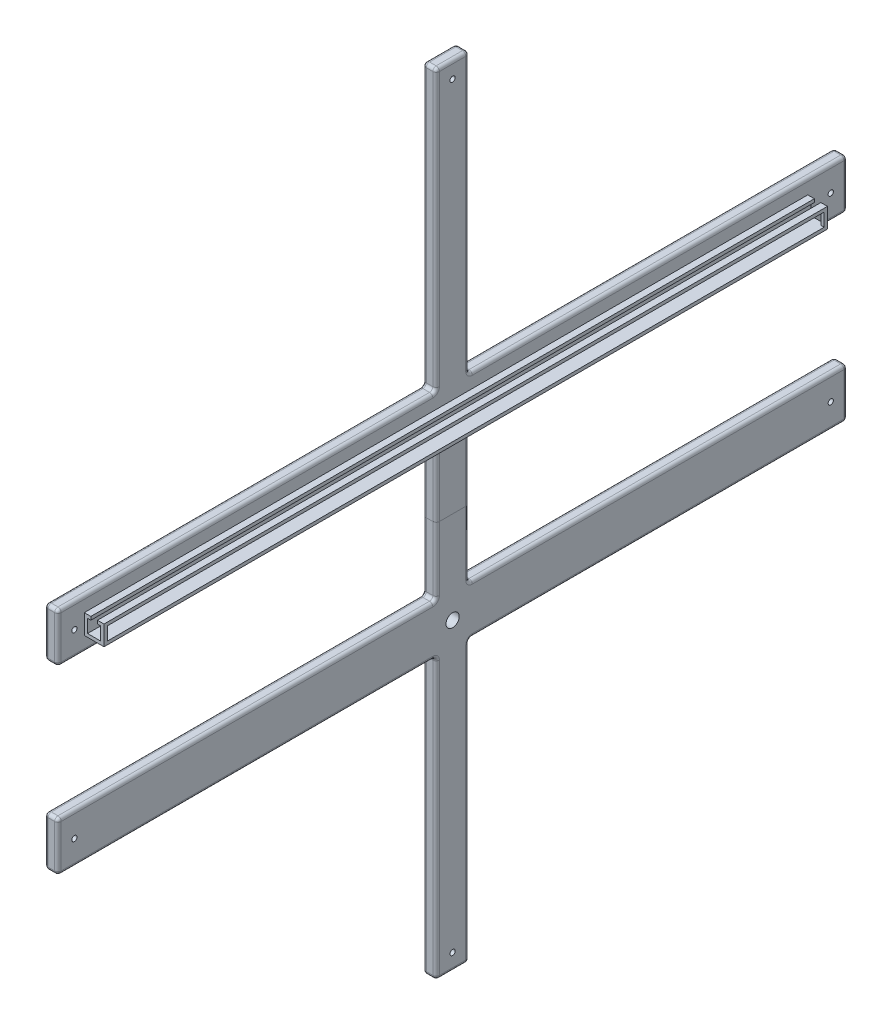
SolidWorks part; units mm, degrees
ref_plane "Front Plane" through (0, 0, 0) normal (0, 0, 1) x (1, 0, 0)
ref_plane "Top Plane" through (0, 0, 0) normal (0, 1, 0) x (1, 0, 0)
ref_plane "Right Plane" through (0, 0, 0) normal (1, 0, 0) x (0, 0, -1)
sketch "Sketch3" plane through (0, 0, 0) normal (1, 0, 0) x (0, 0, -1)
  line L0 (-151.0311, 58.4862) -> (-36.0311, 58.4862)
  line L1 (-276.0311, 3.4862) -> (-161.0311, 3.4862)
  line L2 (-276.0311, 3.4862) -> (-276.0311, -11.5138)
  line L3 (-276.0311, -11.5138) -> (-161.0311, -11.5138)
  line L4 (-36.0311, 3.4862) -> (-36.0311, -11.5138)
  line L5 (-276.0311, 58.4862) -> (-161.0311, 58.4862)
  line L6 (-276.0311, 58.4862) -> (-276.0311, 43.4862)
  line L7 (-276.0311, 43.4862) -> (-161.0311, 43.4862)
  line L8 (-36.0311, 58.4862) -> (-36.0311, 43.4862)
  line L9 (-161.0311, 143.4862) -> (-151.0311, 143.4862)
  line L10 (-161.0311, 143.4862) -> (-161.0311, 58.4862)
  line L11 (-161.0311, -96.5138) -> (-151.0311, -96.5138)
  line L12 (-151.0311, 143.4862) -> (-151.0311, 58.4862)
  line L13 (-151.0311, 43.4862) -> (-36.0311, 43.4862)
  line L14 (-161.0311, 43.4862) -> (-161.0311, 3.4862)
  line L15 (-151.0311, 43.4862) -> (-151.0311, 3.4862)
  line L16 (-151.0311, 3.4862) -> (-36.0311, 3.4862)
  line L17 (-151.0311, -11.5138) -> (-36.0311, -11.5138)
  line L18 (-161.0311, -11.5138) -> (-161.0311, -96.5138)
  line L19 (-151.0311, -11.5138) -> (-151.0311, -96.5138)
  line L20 (-398.8778, 23.4862) -> (82.314, 23.4862) construction
  circle A0 centre (-156.0311, -91.5138) radius 0.8
  circle A2 centre (-156.0311, 138.4862) radius 0.8
  dimension "D9" = 115
  dimension "D13" = 1.6
  dimension "D14" = 5
  dimension "D1" = 240
  dimension "D2" = 240
  dimension "D3" = 240
  dimension "D4" = 10
  dimension "D5" = 15
  dimension "D6" = 15
  dimension "D7" = 85
  dimension "D8" = 85
  dimension "D10" = 115
  dimension "D11" = 115
  dimension "D12" = 40
  dimension "D15" = 5
  dimension "D16" = 120
extrude "Boss-Extrude1" add sketch "Sketch3" along normal blind 4 contours L12 L0 L8 L13 L15 L16 L4 L17 L19 L11 L18 L3 L2 L1 L14 L7 L6 L5 L10 L9
sketch "Sketch4" plane through (0, 0, 0) normal (1, 0, 0) x (0, 0, -1)
  line L0 (-161.0311, -96.5138) -> (-151.0311, -96.5138) construction
  line L1 (-161.0311, -11.5138) -> (-161.0311, -96.5138) construction
  line L2 (-316.8277, 23.4862) -> (27.7287, 23.4862) construction
  line L3 (-161.0311, 143.4862) -> (-151.0311, 143.4862) construction
  line L4 (-156.0311, 175.0015) -> (-156.0311, -131.8525) construction
  line L5 (-151.0311, 143.4862) -> (-151.0311, 58.4862) construction
  line L6 (-276.0311, 3.4862) -> (-276.0311, -11.5138) construction
  line L7 (-276.0311, 3.4862) -> (-161.0311, 3.4862) construction
  line L11 (-276.0311, -11.5138) -> (-161.0311, -11.5138) construction
  line L12 (-161.0311, 43.4862) -> (-161.0311, 3.4862) construction
  circle A0 centre (-156.0311, -91.5138) radius 0.8
  circle A1 centre (-156.0311, 138.4862) radius 0.8
  circle A2 centre (-271.0311, -4.0138) radius 0.8
  circle A3 centre (-271.0311, 50.9862) radius 0.8
  circle A4 centre (-41.0311, -4.0138) radius 0.8
  circle A5 centre (-41.0311, 50.9862) radius 0.8
  circle A6 centre (-156.0311, -4.0138) radius 2
  circle A7 centre (-156.0311, 50.9862) radius 2
  point P10 (-156.0311, 143.4862)
  point P17 (-151.0311, 100.9862)
  dimension "D1" = 1.6
  dimension "D3" = 5
  dimension "D6" = 5
  dimension "D8" = 1.6
  dimension "D9" = 4
  dimension "D10" = 7.5
  dimension "D2" = 5
  dimension "D4" = 120
  dimension "D5" = 5
  dimension "D7" = 7.5
  dimension "D11" = 5
extrude "Cut-Extrude1" cut sketch "Sketch4" against normal blind 4 and the other way blind 4
fillet "Fillet1" radius 1 60 edges at (2, 143.4862, 161.0311) (2, 58.4862, 161.0311) (2, 58.4862, 276.0311) (2, 43.4862, 276.0311) (2, 43.4862, 161.0311) (2, 3.4862, 161.0311) (2, 3.4862, 276.0311) (2, -11.5138, 276.0311) (2, -11.5138, 161.0311) (2, -96.5138, 161.0311) (2, -96.5138, 151.0311) (2, -11.5138, 151.0311) (2, -11.5138, 36.0311) (2, 3.4862, 36.0311) (2, 3.4862, 151.0311) (2, 43.4862, 151.0311) (2, 43.4862, 36.0311) (2, 58.4862, 36.0311) (2, 58.4862, 151.0311) (2, 143.4862, 151.0311) (4, 100.9862, 161.0311) (4, 58.4862, 218.5311) (4, 50.9862, 276.0311) (4, 43.4862, 218.5311) (4, 23.4862, 161.0311) (4, 3.4862, 218.5311) (4, -4.0138, 276.0311) (4, -11.5138, 218.5311) (4, -54.0138, 161.0311) (4, -96.5138, 156.0311) (4, -54.0138, 151.0311) (4, -11.5138, 93.5311) (4, -4.0138, 36.0311) (4, 3.4862, 93.5311) (4, 23.4862, 151.0311) (4, 43.4862, 93.5311) (4, 50.9862, 36.0311) (4, 58.4862, 93.5311) (4, 100.9862, 151.0311) (4, 143.4862, 156.0311) (0, 100.9862, 161.0311) (0, 58.4862, 218.5311) (0, 50.9862, 276.0311) (0, 43.4862, 218.5311) (0, 23.4862, 161.0311) (0, 3.4862, 218.5311) (0, -4.0138, 276.0311) (0, -11.5138, 218.5311) (0, -54.0138, 161.0311) (0, -96.5138, 156.0311) (0, -54.0138, 151.0311) (0, -11.5138, 93.5311) (0, -4.0138, 36.0311) (0, 3.4862, 93.5311) (0, 23.4862, 151.0311) (0, 43.4862, 93.5311) (0, 50.9862, 36.0311) (0, 58.4862, 93.5311) (0, 100.9862, 151.0311) (0, 143.4862, 156.0311)
ref_plane "Plane1" through (4, 0, 0) normal (1, 0, 0) x (0, 0, -1)
ref_plane "Plane2" through (0, 0, 268.0311) normal (0, 0, 1) x (1, 0, 0)
sketch "Sketch6" plane through (0, 0, 268.0311) normal (0, 0, 1) x (1, 0, 0)
  line L0 (4, 57.4862) -> (4, 44.4862) construction
  line L1 (5, 48.9862) -> (9, 48.9862)
  line L3 (4, 47.9862) -> (10, 47.9862)
  line L4 (10, 53.9862) -> (10, 47.9862)
  line L6 (4, 53.9862) -> (4, 47.9862)
  line L9 (4, 47.9862) -> (4.9389, 47.9862)
  line L10 (5, 52.9862) -> (5, 48.9862)
  line L11 (4, 53.9862) -> (6, 53.9862)
  line L13 (5, 52.9862) -> (6, 52.9862)
  line L14 (6, 53.9862) -> (6, 52.9862)
  line L15 (8, 53.9787) -> (10, 53.9787)
  line L16 (8, 53.9787) -> (8, 52.9862)
  line L17 (8, 52.9862) -> (9, 52.9862)
  line L19 (9, 53.9787) -> (10, 53.9787)
  line L20 (9, 52.9862) -> (9, 48.9862)
  line L21 (10.0937, 47.9862) -> (10, 47.9862)
  line L23 (3, 43.4862) -> (1, 43.4862) construction
  line L24 (1, 58.4862) -> (3, 58.4862) construction
  point P0 (0, 0)
  point P23 (2, 43.4862)
  dimension "D1" = 4
  dimension "D2" = 4
  dimension "D3" = 4
  dimension "D4" = 1
  dimension "D5" = 6
  dimension "D6" = 6
  dimension "D7" = 6
  dimension "D8" = 2
  dimension "D9" = 2
  dimension "D10" = 1
  dimension "D11" = 1
  dimension "D12" = 1
  dimension "D13" = 4.5
  dimension "D14" = 4.5
  dimension "D15" = 6
sketch "Sketch7" plane through (0, 0, 268.0311) normal (0, 0, 1) x (1, 0, 0)
  line L0 (6, 53.9862) -> (6, 52.9862)
  line L1 (6, 52.9862) -> (5, 52.9862)
  line L2 (5, 52.9862) -> (5, 48.9862)
  line L3 (5, 48.9862) -> (9, 48.9862)
  line L4 (9, 48.9862) -> (9, 52.9862)
  line L5 (9, 52.9862) -> (8, 52.9862)
  line L6 (8, 52.9862) -> (8, 53.9787)
  line L7 (8, 53.9787) -> (10, 53.9862)
  line L8 (10, 53.9862) -> (10, 47.9862)
  line L9 (10, 47.9862) -> (4, 47.9862)
  line L10 (4, 47.9862) -> (4, 53.9862)
  line L11 (4, 53.9862) -> (6, 53.9862)
extrude "Boss-Extrude5" add sketch "Sketch7" against normal blind 220
ref_plane "Plane3" through (10, 0, 0) normal (1, 0, 0) x (0, 0, -1)
sketch "Sketch9" plane through (10, 0, 0) normal (1, 0, 0) x (0, 0, -1)
  line L0 (-48.0311, 47.9862) -> (-268.0311, 47.9862) construction
  line L1 (-267.0311, 52.9862) -> (-49.0311, 52.9862)
  line L2 (-267.0311, 52.9862) -> (-267.0311, 48.9862)
  line L3 (-267.0311, 48.9862) -> (-49.0311, 48.9862)
  line L4 (-49.0311, 52.9862) -> (-49.0311, 48.9862)
  line L5 (-268.0311, 52.9862) -> (-268.0311, 48.9862) construction
  line L6 (-48.0311, 47.9862) -> (-48.0311, 53.9862) construction
  dimension "D1" = 4
  dimension "D2" = 1
  dimension "D3" = 1
  dimension "D4" = 218
  dimension "D5" = 1
extrude "Cut-Extrude2" cut sketch "Sketch9" against normal blind 2
sketch "Sketch10" plane through (4, 0, 0) normal (1, 0, 0) x (0, 0, -1)
  line L0 (-257.3659, 23.9862) -> (-36.5246, 23.9862) construction
  line L1 (-150.0311, 44.4862) -> (-37.0311, 44.4862) construction
  line L2 (-150.0311, 3.4862) -> (-37.0311, 3.4862) construction
  dimension "D1" = 20.5
  dimension "D2" = 20.5
ref_plane "Plane5" through (0, 23.9862, 0) normal (0, -1, 0) x (0, 0, -1)
split "Split1" trim tools "Plane5" bodies to split 106 resulting bodies 111 112
